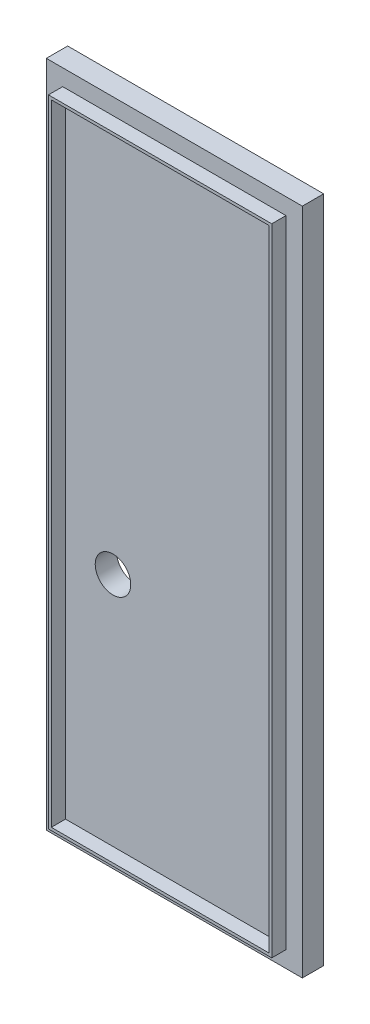
SolidWorks part; units mm, degrees
ref_plane "Front Plane" through (0, 0, 0) normal (0, 0, 1) x (1, 0, 0)
ref_plane "Top Plane" through (0, 0, 0) normal (0, 1, 0) x (1, 0, 0)
ref_plane "Right Plane" through (0, 0, 0) normal (1, 0, 0) x (0, 0, -1)
sketch "Sketch1" plane through (0, 0, 0) normal (0, 0, 1) x (1, 0, 0)
  line L1 (-87.5559, 76.1562) -> (-41.8359, 76.1562)
  line L2 (-87.5559, 76.1562) -> (-87.5559, -43.2238)
  line L3 (-87.5559, -43.2238) -> (-41.8359, -43.2238)
  line L4 (-41.8359, 76.1562) -> (-41.8359, -43.2238)
  line L5 (-84.9905, 73.5908) -> (-44.4013, 73.5908)
  line L6 (-84.9905, 73.5908) -> (-84.9905, -40.6584)
  line L7 (-84.9905, -40.6584) -> (-44.4013, -40.6584)
  line L8 (-44.4013, 73.5908) -> (-44.4013, -40.6584)
  line L9 (-84.4825, 73.0828) -> (-44.9093, 73.0828)
  line L10 (-84.4825, 73.0828) -> (-84.4825, -40.1504)
  line L11 (-84.4825, -40.1504) -> (-44.9093, -40.1504)
  line L12 (-44.9093, 73.0828) -> (-44.9093, -40.1504)
  dimension "D1" = 119.38
  dimension "D2" = 45.72
  dimension "D3" = 2.5654
  dimension "D4" = 2.5654
  dimension "D5" = 2.5654
  dimension "D6" = 2.5654
  dimension "D7" = 0.508
  dimension "D8" = 0.508
  dimension "D9" = 0.508
  dimension "D10" = 0.508
extrude "Boss-Extrude1" add sketch "Sketch1" along normal blind 3.81 contours L2 L3 L4 L1
sketch "Sketch2" plane through (0, 0, 3.81) normal (0, 0, 1) x (1, 0, 0)
  line L0 (-87.5559, 76.1562) -> (-41.8359, 76.1562) construction
  line L1 (-84.6349, 73.2352) -> (-44.7569, 73.2352)
  line L2 (-84.6349, 73.2352) -> (-84.6349, -40.3028)
  line L3 (-84.6349, -40.3028) -> (-44.7569, -40.3028)
  line L4 (-44.7569, 73.2352) -> (-44.7569, -40.3028)
  line L5 (-41.8359, 76.1562) -> (-41.8359, -43.2238) construction
  line L6 (-87.5559, -43.2238) -> (-41.8359, -43.2238) construction
  line L7 (-87.5559, 76.1562) -> (-87.5559, -43.2238) construction
  line L9 (-84.1269, 72.7272) -> (-45.2649, 72.7272)
  line L10 (-84.1269, 72.7272) -> (-84.1269, -39.7948)
  line L11 (-84.1269, -39.7948) -> (-45.2649, -39.7948)
  line L12 (-45.2649, 72.7272) -> (-45.2649, -39.7948)
  dimension "D1" = 2.921
  dimension "D2" = 2.921
  dimension "D3" = 2.921
  dimension "D4" = 2.921
  dimension "D5" = 0.508
  dimension "D6" = 0.508
  dimension "D7" = 0.508
  dimension "D8" = 0.508
extrude "Boss-Extrude2" add sketch "Sketch2" along normal blind 2.54
sketch "Sketch4" plane through (0, 0, 0) normal (0, 0, -1) x (-1, 0, 0)
  line L0 (87.5559, 76.1562) -> (87.5559, -43.2238) construction
  line L1 (87.5559, -43.2238) -> (41.8359, -43.2238) construction
  circle A0 centre (75.6509, 2.2752) radius 3.175
  dimension "D1" = 6.35
  dimension "D2" = 11.905
  dimension "D3" = 45.499
extrude "Cut-Extrude1" cut sketch "Sketch4" against normal through all
